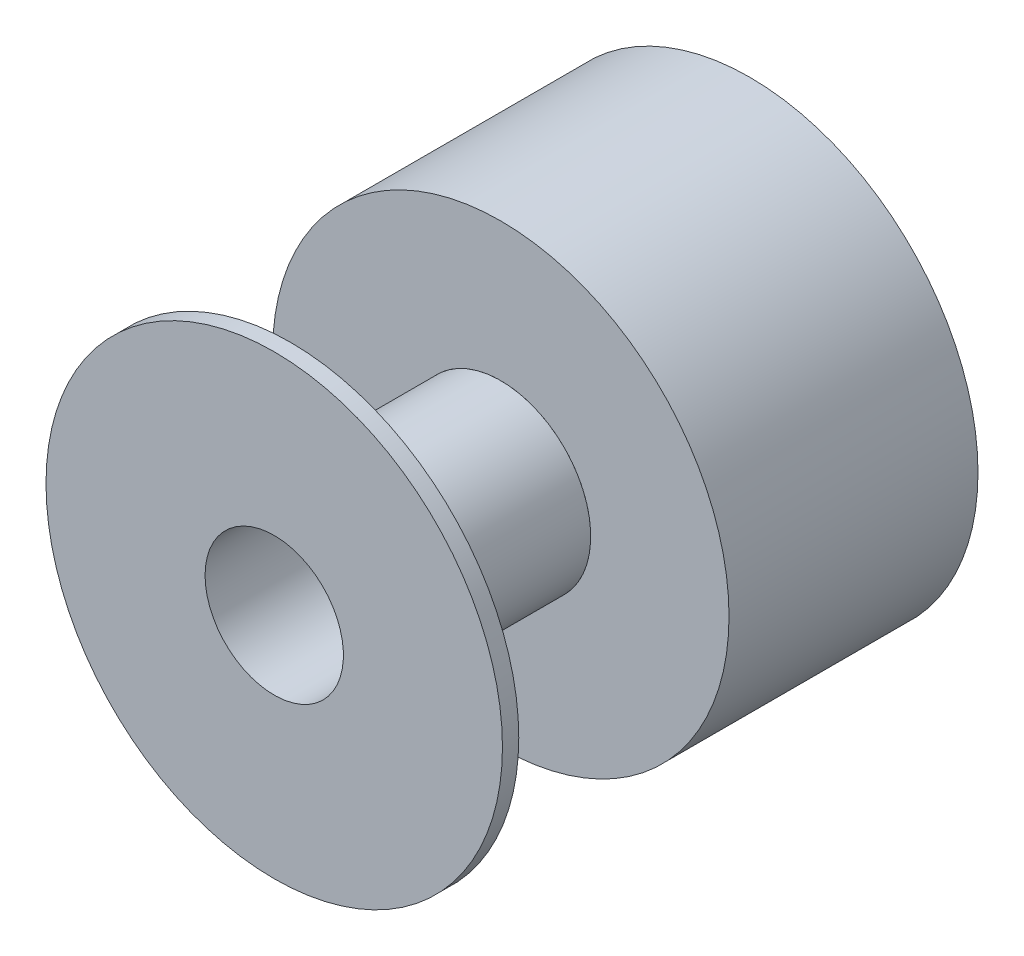
SolidWorks part; units mm, degrees
material "Plain Carbon Steel"
ref_plane "Front Plane" through (0, 0, 0) normal (0, 0, 1) x (1, 0, 0)
ref_plane "Top Plane" through (0, 0, 0) normal (0, 1, 0) x (1, 0, 0)
ref_plane "Right Plane" through (0, 0, 0) normal (1, 0, 0) x (0, 0, -1)
sketch "Sketch1" plane through (0, 0, 0) normal (0, 0, 1) x (1, 0, 0)
  circle A0 centre (0, 0) radius 8.25
  circle A1 centre (0, 0) radius 2.5
  circle A2 centre (0, 0) radius 3.25
  dimension "D1" = 16.5
  dimension "D2" = 5
  dimension "D3" = 6.5
extrude "Boss-Extrude1" add sketch "Sketch1" along normal blind 7.6 contours A2 A1 region at (-3.1581, 0, 0)
extrude "Boss-Extrude2" add sketch "Sketch1<3>" against normal blind 9 separate body contours A0 A2 region at (-8.0167, 0, 0)
sketch "Sketch1<3>" plane through (0, 0, 0) normal (0, 0, 1) x (1, 0, 0) same geometry as "Sketch1"
sketch "Sketch2" plane through (0, 0, 7.6) normal (0, 0, 1) x (1, 0, 0)
  circle A0 centre (0, 0) radius 8.25
  circle A1 centre (0, 0) radius 8.25 construction
  circle A2 centre (0, 0) radius 2.5
extrude "Boss-Extrude3" add sketch "Sketch2" along normal blind 0.59
